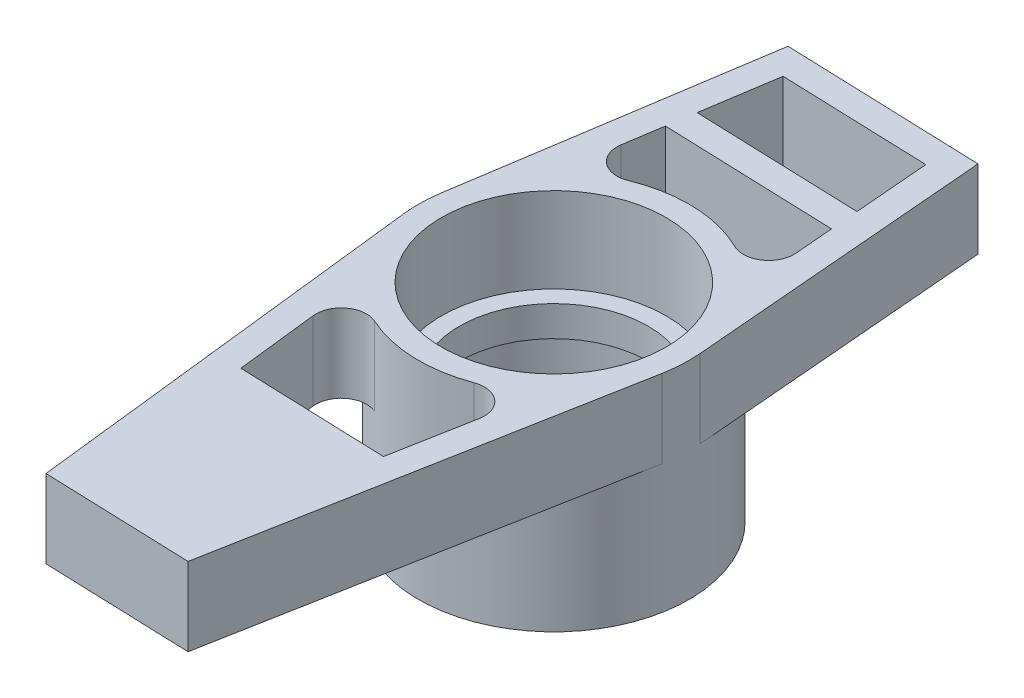
SolidWorks part; units mm, degrees
other "Markup1"
sketch "Sketch29" plane through (63.2714, 21.9964, 116.8802) normal (1, 0, 0) x (0, 0, 1)
material "6061-T6 (SS)"
ref_plane "X-Y Datum" through (0, 0, 0) normal (0, 0, 1) x (1, 0, 0)
ref_plane "X-Z Datum" through (0, 0, 0) normal (0, 1, 0) x (1, 0, 0)
ref_plane "Y-Z Datum" through (0, 0, 0) normal (1, 0, 0) x (0, 0, -1)
sketch "Main skeleton" plane through (0, 0, 0) normal (1, 0, 0) x (0, 0, -1)
  line L0 (0, 0) -> (-39.9854, 0) construction
  line L1 (0, 0) -> (0, -60.6196) construction
  line L2 (0, 21.9964) -> (-30.2613, 21.9964) construction
  line L3 (-84.7344, 21.9964) -> (-84.7344, -57.7596) construction
  line L4 (69.85, 21.9964) -> (69.85, -22.7076) construction
  line L5 (58.6559, -10.541) -> (-36.2694, -10.541) construction
  line L6 (69.85, -22.7076) -> (-84.7344, -57.7596) construction
  line L7 (27.94, -25.5016) -> (27.94, -201.1028) construction
  circle A0 centre (-84.7344, -57.7596) radius 10.3251 construction
  circle A1 centre (69.85, -22.7076) radius 10.3251 construction
  point P7 (-84.7344, 21.9964)
  point P12 (69.85, 21.9964)
  point P19 (27.94, -66.9036)
  dimension "D4" = 20.6502
  dimension "D1" = 21.9964
  dimension "D2" = 84.7344
  dimension "D3" = 79.756
  dimension "D5" = 69.85
  dimension "D6" = 44.704
  dimension "D7" = 32.5374
  dimension "D8" = 27.94
  dimension "D9" = 88.9
ref_plane "Toe Bracket Plane" through (0, 0, -27.94) normal (0, 0, 1) x (1, 0, 0)
sketch "Toe Bracket Sketch" plane through (0, 0, -27.94) normal (0, 0, 1) x (1, 0, 0)
  line L0 (0, -66.9036) -> (-65.278, -66.9036) construction
  dimension "D1" = 65.278
ref_plane "Back of Upright" through (0, -10.541, 0) normal (0, -1, 0) x (-1, 0, 0)
ref_plane "Plane2" through (0, -57.7596, 84.7344) normal (0, -1, 0) x (-1, 0, 0)
sketch "Caster Angle" plane through (0, -57.7596, 84.7344) normal (0, -1, 0) x (-1, 0, 0)
  line L0 (0, 0) -> (2.959, 0) construction
  line L1 (0, 154.5844) -> (-2.4392, 154.5844) construction
  line L2 (-2.4392, 154.5844) -> (2.959, 0) construction
  line L3 (0, 200084.7344) -> (0, -199945.5269) construction
  point P15 (0, 84.7344)
  dimension "D1" = 2
ref_plane "Caster Plane" through (0, 0, 0) normal (0.9994, 0, 0.0349) x (0.0349, 0, -0.9994)
sketch "UBJ LBJ Caster" plane through (0, 0, 0) normal (0.9994, 0, 0.0349) x (0.0349, 0, -0.9994)
  circle A0 centre (-84.786, -57.7596) radius 10.3251 construction
  circle A1 centre (69.8074, -22.7076) radius 10.3251 construction
  dimension "D1" = 20.6502
  dimension "D2" = 20.6502
sketch "Brake Tabs + Speed Sensor" plane through (0, -10.541, 0) normal (0, -1, 0) x (-1, 0, 0)
  line L0 (0, 0) -> (-55.6175, -1.9422) construction
  line L1 (-2.4392, 69.85) -> (2.959, -84.7344) construction
  line L2 (-57.2927, 46.0282) -> (-53.9423, -49.9126) construction
  line L3 (0, 0) -> (43.5133, -16.7032) construction
  line L4 (0, 200000) -> (0, -200030.2613) construction
  point P5 (39.1559, -25.2827)
  point P9 (-55.6175, -1.9422)
  point P12 (39.0896, -25.3851)
  dimension "D1" = 55.6514
  dimension "D2" = 95.9993
  dimension "D3" = 46.609
  dimension "D4" = 69
sketch "Main Body" plane through (0, -10.541, 0) normal (0, -1, 0) x (-1, 0, 0)
  line L0 (36.9042, 5.6919) -> (24.0965, 88.7327)
  line L1 (-30.2275, 86.8357) -> (24.0965, 88.7327)
  line L2 (71.628, 16.8275) -> (53.848, 16.8275)
  line L3 (71.628, 39.0525) -> (53.848, 39.0525)
  line L4 (-2.4392, 69.85) -> (2.959, -84.7344) construction
  line L5 (-30.2275, 86.8357) -> (-37.2113, 3.1037)
  line L6 (40.4492, -23.5062) -> (36.9753, -21.9416)
  line L7 (20.7672, 60.329) -> (-24.9249, 58.7334)
  line L8 (0, 27.94) -> (65.278, 27.94) construction
  line L15 (-23.1965, 79.4565) -> (17.5974, 80.8811)
  line L16 (65.278, 39.0525) -> (65.278, 16.8275) construction
  line L17 (20.7672, 60.329) -> (17.5974, 80.8811)
  line L18 (-24.9249, 58.7334) -> (-23.1965, 79.4565)
  line L19 (-2.4392, 69.85) -> (-2.0789, 59.5312) construction
  line L20 (-2.4392, 69.85) -> (-2.7996, 80.1688) construction
  line L21 (23.5731, 42.1363) -> (21.9369, 52.7452)
  line L22 (21.9369, 52.7452) -> (-25.5628, 51.0865)
  line L23 (-25.5628, 51.0865) -> (-26.455, 40.3893)
  line L24 (0, 200000) -> (0, -200030.2613) construction
  line L25 (71.628, 39.0525) -> (71.628, 44.1325)
  line L26 (71.628, 44.1325) -> (44.6271, 44.1325)
  line L27 (71.628, 16.8275) -> (71.628, 11.7475)
  line L28 (71.628, 11.7475) -> (46.1421, 11.7475)
  line L29 (37.0998, -4.2332) -> (24.3747, -115.7559)
  line L30 (-36.7141, -6.8109) -> (-16.2406, -117.1742)
  line L31 (24.3747, -115.7559) -> (-16.2406, -117.1742)
  line L32 (25.2152, -41.1747) -> (22.6433, -63.7146)
  line L33 (-22.2816, -42.8333) -> (-18.1437, -65.1389)
  line L34 (22.6433, -63.7146) -> (-18.1437, -65.1389)
  line L35 (-47.2194, -55.3475) -> (-35.8532, -41.2874)
  line L36 (-50.3895, 51.2323) -> (-41.5847, 39.5527)
  line L37 (-61.9097, -46.5573) -> (-47.2691, -11.7926)
  line L38 (-65.0065, 42.1253) -> (-47.9766, 8.4665)
  line L39 (-22.2816, -42.8333) -> (25.2152, -41.1747) construction
  circle A0 centre (0, 0) radius 30.9905
  circle A1 centre (0, 0) radius 26.0375
  circle A2 centre (0, 0) radius 37.3405
  arc A3 (53.848, 16.8275) -> (53.848, 39.0525) centre (53.848, 27.94) cw
  arc A4 (23.5731, 42.1363) -> (14.0429, 34.5993) centre (16.6698, 41.0716) cw
  arc A5 (-26.455, 40.3893) -> (-16.4222, 33.5355) centre (-19.4942, 39.8087) ccw
  arc A6 (44.6271, 44.1325) -> (32.4395, 38.7599) centre (44.6271, 27.6225) ccw
  arc A7 (32.4395, 38.7599) -> (14.0429, 34.5993) centre (20.2519, 49.8973) cw
  arc A8 (46.1421, 11.7475) -> (37.2691, 2.308) centre (46.1421, 2.8575) ccw
  arc A9 (25.2152, -41.1747) -> (15.3954, -34.0191) centre (18.2752, -40.3828) ccw
  arc A10 (-22.2816, -42.8333) -> (-12.9848, -35.0102) centre (-15.4138, -41.5592) cw
  circle A11 centre (-53.9423, -49.9126) radius 4.2
  circle A12 centre (-57.2927, 46.0282) radius 4.2
  arc A13 (-47.2194, -55.3475) -> (-61.9097, -46.5573) centre (-53.9423, -49.9126) cw
  arc A14 (-50.3895, 51.2323) -> (-65.0065, 42.1253) centre (-57.2927, 46.0282) ccw
  arc A15 (-35.8532, -41.2874) -> (-12.9848, -35.0102) centre (-20.0509, -54.062) cw
  arc A16 (-41.5847, 39.5527) -> (-16.4222, 33.5355) centre (-25.3588, 51.7848) ccw
  arc A17 (-47.2691, -11.7926) -> (-47.9766, 8.4665) centre (-69.5075, -2.4273) ccw
  circle A18 centre (43.5133, -16.7032) radius 5.5562
  arc A19 (40.4492, -23.5062) -> (43.9026, -9.2521) centre (43.5133, -16.7032) ccw
  arc A20 (43.9026, -9.2521) -> (37.2913, -1.9178) centre (44.267, -2.2766) cw
  arc A21 (36.9753, -21.9416) -> (28.7321, -23.8492) centre (34.1068, -28.3104) ccw
  point P14 (-2.0789, 59.5312)
  point P19 (-3.0655, 87.7842)
  point P20 (-2.7996, 80.1688)
  point P35 (-1.8129, 51.9158)
  point P36 (65.278, 27.94)
  point P40 (65.278, 27.94)
  point P60 (4.067, -116.4651)
  point P64 (2.2498, -64.4268)
  point P73 (43.5133, -16.7032)
  point P96 (0, 0)
  point P97 (0, 0)
  point P100 (0, 0)
  point P101 (0, 0)
  point P102 (0, 0)
  point P103 (1.4668, -42.004)
  point P104 (0, 0)
  dimension "D4" = 20.6502
  dimension "D1" = 61.9811
  dimension "D16" = 6.985
  dimension "D14" = 16.51
  dimension "D17" = 8.89
  dimension "D22" = 6.985
  dimension "D23" = 8.4
  dimension "D26" = 20.32
  dimension "D27" = 24.13
  dimension "D29" = 11.1125
  dimension "D31" = 6.985
  dimension "D2" = 6.35
  dimension "D6" = 7.62
  dimension "D7" = 7.62
  dimension "D8" = 7.62
  dimension "D5" = 22.86
  dimension "D10" = 22.225
  dimension "D11" = 65.278
  dimension "D12" = 6.35
  dimension "D13" = 11.43
  dimension "D15" = 5.08
  dimension "D18" = 31.75
  dimension "D19" = 20.32
  dimension "D20" = 7.62
  dimension "D21" = 20.32
  dimension "D24" = 4.445
  dimension "D25" = 4.445
  dimension "D28" = 37.7218
  dimension "D30" = 1.905
  dimension "D33" = 3.81
extrude "Boss-Extrude1" add sketch "Main Body" along normal blind 57.15 contours A0 A1 | A2 A0 region at (-36.0752, -10.541, -3.8908) region at (30.114, -10.541, 0)
extrude "Cut-Extrude2" cut sketch "Main Body<5>" along normal blind 23.495 contours A0 A1 region at (30.114, -10.541, 0)
sketch "Main Body<5>" plane through (0, -10.541, 0) normal (0, -1, 0) x (-1, 0, 0) same geometry as "Main Body"
extrude "Cut-Extrude3" cut sketch "Main Body<6>" against normal blind 25.273 from surface contours A0 A1 region at (30.114, -10.541, 0) starting at face at (0, -67.691, -26.0375)
sketch "Main Body<6>" plane through (0, -10.541, 0) normal (0, -1, 0) x (-1, 0, 0) same geometry as "Main Body"
extrude "Boss-Extrude2" add sketch "Main Body<7>" along normal blind 21.59 contours L5 A16 A5 L23 L22 L21 A4 A7 L0 L1 L7 L18 L15 L17 | L0 A7 A2 | A16 L5 A2 region at (-29.1607, -10.541, -28.0492) region at (-23.3339, -10.541, -34.5721) region at (31.132, -10.541, -25.2821)
sketch "Main Body<7>" plane through (0, -10.541, 0) normal (0, -1, 0) x (-1, 0, 0) same geometry as "Main Body"
extrude "Boss-Extrude3" add sketch "Main Body<8>" along normal blind 21.59 contours L30 A15 A2 | A15 L30 L31 L29 A2 A9 L32 L34 L33 A10 | A21 L29 A2 region at (-34.0942, -10.541, 17.4427) region at (28.4465, -10.541, 28.2698) region at (-3.7625, -10.541, 80.3793)
sketch "Main Body<8>" plane through (0, -10.541, 0) normal (0, -1, 0) x (-1, 0, 0) same geometry as "Main Body"
sketch "Sketch30" plane through (0, 0, 0) normal (0.9994, 0, 0.0349) x (0.0349, 0, -0.9994)
  line L0 (-42.0296, -32.131) -> (-42.0296, -10.541) construction
  line L1 (-52.2089, -10.541) -> (52.2089, -10.541) construction
  line L2 (-64.466, -10.541) -> (-64.466, -16.891) construction
  line L3 (-42.0296, -32.131) -> (-64.466, -16.891)
  line L4 (-64.466, -16.891) -> (-116.536, -27.4789)
  line L5 (-116.536, -10.541) -> (-116.536, -27.4789) construction
  line L7 (-116.536, -32.131) -> (-116.536, -10.541) construction
  line L8 (-116.536, -27.4789) -> (-116.536, -32.131)
  line L9 (-5.5254, -10.541) -> (-116.536, -10.541) construction
  line L10 (-116.536, -32.131) -> (-42.0296, -32.131)
  line L11 (-116.536, -10.541) -> (-116.536, -19.7938)
  line L12 (-116.536, -19.7938) -> (-71.0323, -10.541)
  line L13 (-71.0323, -10.541) -> (-116.536, -10.541)
  point P5 (-116.536, -27.4789)
equation "\"upper ball joint X\"= 3.14in"
equation "\"upper ball joint Y\"= 3.336"
equation "\"lower ball joint X\"= 1.76"
equation "\"lower ball joint Y\"= 2.75in"
equation "\"D3@Main skeleton\"=\"upper ball joint X\""
equation "\"D2@Main skeleton\"=\"upper ball joint Y\""
equation "\"D5@Main skeleton\"=\"lower ball joint Y\""
equation "\"D6@Main skeleton\"=\"lower ball joint X\""
equation "\"wheel offset to back of upright\"= 1.281in"
equation "\"D7@Main skeleton\"=\"wheel offset to back of upright\""
equation "\"Toe bracket distance from center Z\"= 1.1"
equation "\"D8@Main skeleton\"=\"Toe bracket distance from center Z\""
equation "\"Toe bracket distance from hub face Y\"= 3.5in"
equation "\"D9@Main skeleton\"=\"Toe bracket distance from hub face Y\""
equation "\"Toe Bracket distance in X\"= 2.57in"
equation "\"Caster\"= 2.5deg"
equation "\"Spacing Between UBJ/LBJ\"= 0.813in"
equation "\"Toe Bracket Spacing\"= 0.875in"
equation "\"D4@Main skeleton\"=\"Spacing Between UBJ/LBJ\""
equation "\"1/4 bolt\"= .25in"
equation "\"3/8 Bolt\"= 5 / 16"
equation "\"Back of upright face LBJ 1\"= .5in"
equation "\"Back of upright face LBJ 2\"= .9in"
equation "\"Back of upright face UBJ 1\"= .9in"
equation "\"UBJ Y1\"= 1in"
equation "\"UBJ Y2\"= .5in"
equation "\"LBJ Double shear thickness\"= .275in"
equation "\"LBJ fucking slant shit\"= .03in"
equation "\"Brake mounting holes parallel\"= 03.7795in"
equation "\"Brake mounting holes normal\"= 02.191in"
equation "\"Speed sensor radial distance\"= 01.835in"
equation "\"Speed sensor hold diameter\"= 0.46875in"
equation "\"D1@UBJ LBJ Caster\" = \"Spacing Between UBJ/LBJ\""
equation "\"D2@UBJ LBJ Caster\" = \"Spacing Between UBJ/LBJ\""
equation "\"D1@Toe Bracket Sketch\" = \"Toe Bracket distance in X\""
equation "\"D1@Brake Tabs + Speed Sensor\" = \"Brake mounting holes normal\""
equation "\"D2@Brake Tabs + Speed Sensor\" = \"Brake mounting holes parallel\""
equation "\"D4@Main Body\"=\"Spacing Between UBJ/LBJ\""
equation "\"D10@Main Body\"=\"Toe Bracket Spacing\""
equation "\"D11@Main Body\"=\"Toe Bracket distance in X\""
equation "\"D3@Brake Tabs + Speed Sensor\"=\"Speed sensor radial distance\""
equation "\"UBJ Main Body Extrude Distance\"= .85in"
equation "\"D1@Boss-Extrude3\"=\"UBJ Main Body Extrude Distance\""
equation "\"D1@Sketch30\"=\"UBJ Main Body Extrude Distance\""
equation "\"D4@Sketch30\"=\"UBJ Main Body Extrude Distance\""
